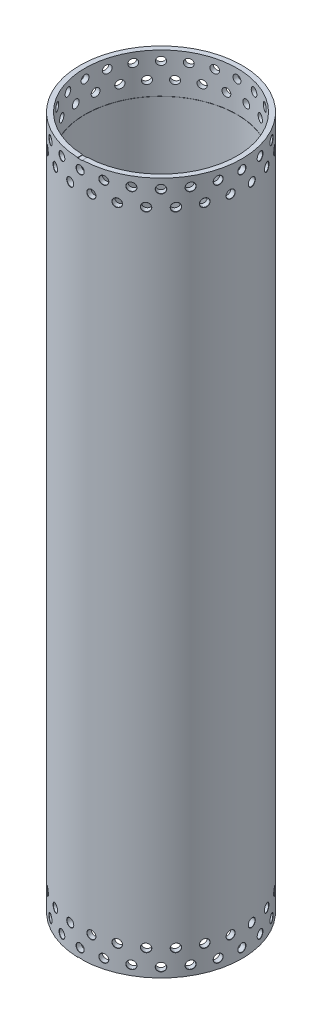
SolidWorks part; units mm, degrees
material "AW-6082-T6 (PA4)"
ref_plane "Płaszczyzna przednia" through (0, 0, 0) normal (0, 0, 1) x (1, 0, 0)
ref_plane "Płaszczyzna górna" through (0, 0, 0) normal (0, 1, 0) x (1, 0, 0)
ref_plane "Płaszczyzna prawa" through (0, 0, 0) normal (1, 0, 0) x (0, 0, -1)
sketch "Szkic1" plane through (0, 0, 0) normal (0, 1, 0) x (1, 0, 0)
  circle A0 centre (0, 0) radius 90
  circle A1 centre (0, 0) radius 81.5
  dimension "D1" = 8.5
  dimension "D2" = 180
  dimension "D3" = 163
extrude "Dodanie-wyciągnięcie1" add sketch "Szkic1" along normal blind 744
sketch "Szkic2" plane through (0, 744, 0) normal (0, 1, 0) x (1, 0, 0)
  circle A0 centre (0, 0) radius 87
  circle A1 centre (0, 0) radius 90 construction
  circle A2 centre (0, 0) radius 90
  dimension "D1" = 174
extrude "Wytnij-wyciągnięcie1" cut sketch "Szkic2" against normal through all
sketch "Szkic3" plane through (0, 744, 0) normal (0, 1, 0) x (1, 0, 0)
  circle A0 centre (0, 0) radius 81.7
  circle A1 centre (0, 0) radius 81.5 construction
  circle A2 centre (0, 0) radius 81.5
  dimension "D1" = 0.2
extrude "Wytnij-wyciągnięcie2" cut sketch "Szkic3" against normal blind 43
ref_plane "Płaszczyzna1" through (0, 0, 87) normal (0, 0, 1) x (1, 0, 0)
ref_plane "Płaszczyzna2" through (11.3558, 0, 86.2557) normal (0.1305, 0, 0.9914) x (0, 1, 0)
hole_wizard "Otwór Ø8.5 (8.5)1" positions "Szkic5" profile "Szkic6" hole size "Ø8.5" standard "DIN" end condition up to next
sketch "Szkic5" plane through (0, 0, 87) normal (0, 0, 1) x (1, 0, 0)
  line L0 (87, 744) -> (-87, 744) construction
  line L1 (87, 0) -> (87, 744) construction
  line L2 (-87, 744) -> (-87, 0) construction
  line L3 (87, 0) -> (87, 744)
  line L4 (-87, 744) -> (-87, 0)
  line L5 (0, 869.2816) -> (0, 760.9563) construction
  point P0 (0, 733.8)
  dimension "D1" = 10.2
sketch "Szkic6" plane through (0, 733.8, 87) normal (1, 0, 0) x (0, -1, 0)
  line L0 (0, 0) -> (0, 5.3)
  line L1 (0, 5.3) -> (4.25, 5.3)
  line L2 (4.25, 5.3) -> (4.25, 0.25)
  line L3 (4.25, 0.25) -> (4.5, 0)
  line L5 (4.5, 0) -> (0, 0)
  line L6 (-4.25, 0.25) -> (-4.5, 0) construction
  line L11 (0, -6.35) -> (0, 107.95) construction
  dimension "Średnica otworu na wylot" = 8.5
  dimension "Głębokość otworu na wylot" = 5.3
  dimension "Średnica zewnętrznego pogłębienia stożkowego" = 9
  dimension "Kąt zewnętrznego pogłębienia stożkowego" = 90
hole_wizard "Otwór Ø8.5 (8.5)2" positions "Szkic7" profile "Szkic8" hole size "Ø8.5" standard "BSI" end condition up to next
sketch "Szkic7" plane through (11.3558, 0, 86.2557) normal (0.1305, 0, 0.9914) x (0, 1, 0)
  line L0 (744, -87) -> (744, 87) construction
  line L1 (0, -87) -> (744, -87) construction
  line L2 (744, 87) -> (0, 87) construction
  line L3 (0, -87) -> (744, -87)
  line L4 (744, 87) -> (0, 87)
  line L5 (862.9512, 0) -> (744.0524, 0) construction
  ellipse E0 centre (733.8, 11.3231) end of major axis (738.05, 11.3231) minor radius 4.2136 construction
  point P0 (716.5, 0)
  dimension "D1" = 27.5
  dimension "D2" = 20.6762
sketch "Szkic8" plane through (11.3558, 716.5, 86.2557) normal (0, 1, 0) x (0.9914, 0, -0.1305)
  line L0 (0, 0) -> (0, 5.3)
  line L1 (0, 5.3) -> (4.25, 5.3)
  line L2 (4.25, 5.3) -> (4.25, 0.25)
  line L3 (4.25, 0.25) -> (4.5, 0)
  line L5 (4.5, 0) -> (0, 0)
  line L6 (-4.25, 0.25) -> (-4.5, 0) construction
  line L11 (0, -6.35) -> (0, 107.95) construction
  dimension "Średnica otworu na wylot" = 8.5
  dimension "Głębokość otworu na wylot" = 5.3
  dimension "Średnica zewnętrznego pogłębienia stożkowego" = 9
  dimension "Kąt zewnętrznego pogłębienia stożkowego" = 90
sketch "Szkic9" plane through (0, 744, 0) normal (0, 1, 0) x (1, 0, 0)
  line L0 (0, -87) -> (0, -1.7049) construction
  line L1 (2.5, -86.9641) -> (2.5, -81.4616)
  line L2 (-2.5, -86.9641) -> (-2.5, -81.4616)
  circle A0 centre (0, 0) radius 87 construction
  circle A1 centre (0, 0) radius 81.5 construction
  circle A2 centre (0, 0) radius 87
  circle A3 centre (0, 0) radius 81.5
  circle M6 centre (0, 0) radius 81.7
  circle M7 centre (0, 0) radius 87
  dimension "D1" = 5
extrude "Wytnij-wyciągnięcie3" cut sketch "Szkic9" against normal blind 0.5 contours L0 A2 L1 M6 | L0 L2 M7 M6 region at (-1.2501, 744, 84.3376) region at (1.2501, 744, 84.3376)
pattern_circular "Szyk kołowy1" count 24 over 360 about axis through (0, 0, 0) along (0, 1, 0) of "Otwór Ø8.5 (8.5)1", "Otwór Ø8.5 (8.5)2" reverse direction yes
ref_plane "Płaszczyzna3" through (0, 372, 0) normal (0, 1, 0) x (1, 0, 0)
mirror "Lustro1" about plane through (0, 372, 0) normal (0, 1, 0) of "Wytnij-wyciągnięcie3", "Wytnij-wyciągnięcie2", "Szyk kołowy1", "Otwór Ø8.5 (8.5)1", "Otwór Ø8.5 (8.5)2"
